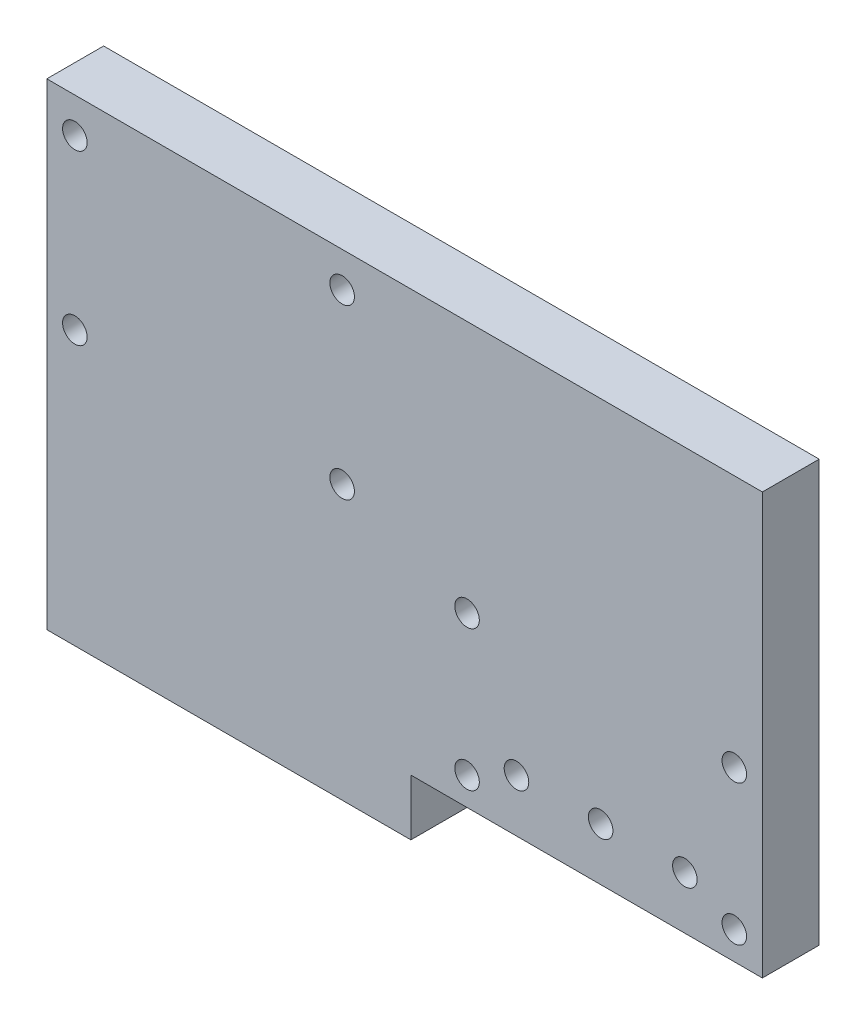
SolidWorks part; units mm, degrees
ref_plane "Plan de face" through (0, 0, 0) normal (0, 0, 1) x (1, 0, 0)
ref_plane "Plan de dessus" through (0, 0, 0) normal (0, 1, 0) x (1, 0, 0)
ref_plane "Plan de droite" through (0, 0, 0) normal (1, 0, 0) x (0, 0, -1)
sketch "Esquisse1" plane through (0, 0, 0) normal (0, 0, 1) x (1, 0, 0)
  line L1 (0, 0) -> (102, 0)
  line L2 (0, 0) -> (0, 60)
  line L3 (0, 60) -> (102, 60)
  line L4 (102, 0) -> (102, 60)
  dimension "D1" = 102
  dimension "D2" = 60
extrude "Boss.-Extru.1" add sketch "Esquisse1" along normal blind 8.1
sketch "Esquisse2" plane through (0, 0, 8.1) normal (0, 0, 1) x (1, 0, 0)
  line L0 (4, 31) -> (4, 55) construction
  line L1 (0, 60) -> (0, 0) construction
  line L2 (102, 60) -> (0, 60) construction
  line L3 (98, 4) -> (98, 24) construction
  line L4 (0, 0) -> (102, 0) construction
  line L5 (102, 0) -> (102, 60) construction
  line L6 (78.95, 0) -> (78.95, 26.94) construction
  line L7 (59.9, 4) -> (59.9, 24) construction
  line L8 (23.05, 60) -> (23.05, 33.0789) construction
  line L9 (42.1, 31) -> (42.1, 55) construction
  line L10 (78.95, 7.5) -> (66.95, 7.5) construction
  circle A0 centre (4, 55) radius 1.75
  circle A1 centre (4, 31) radius 1.75
  circle A2 centre (98, 24) radius 1.75
  circle A3 centre (98, 4) radius 1.75
  circle A4 centre (59.9, 4) radius 1.75
  circle A5 centre (59.9, 24) radius 1.75
  circle A6 centre (42.1, 31) radius 1.75
  circle A7 centre (42.1, 55) radius 1.75
  circle A8 centre (66.95, 7.5) radius 1.75
  circle A9 centre (78.95, 7.5) radius 1.75
  circle A10 centre (90.95, 7.5) radius 1.75
  dimension "D1" = 3.5
  dimension "D2" = 4
  dimension "D11" = 12
  dimension "D12" = 3.5
  dimension "D3" = 5
  dimension "D4" = 24
  dimension "D5" = 4
  dimension "D6" = 4
  dimension "D7" = 20
  dimension "D8" = 38.1
  dimension "D9" = 38.1
  dimension "D10" = 7.5
extrude "Enlèv. mat.-Extru.1" cut sketch "Esquisse2" against normal through all
sketch "Esquisse5" plane through (0, 0, 8.1) normal (0, 0, 1) x (1, 0, 0)
  line L0 (102, 0) -> (102, 60) construction
  line L1 (0, 0) -> (51.9, 0)
  line L2 (0, 0) -> (0, -8)
  line L3 (0, -8) -> (51.9, -8)
  line L4 (51.9, 0) -> (51.9, -8)
  dimension "D1" = 8
  dimension "D2" = 50.1
extrude "Boss.-Extru.2" add sketch "Esquisse5" against normal up to vertex (8.1 mm away) up to point (0, 0, 0)
